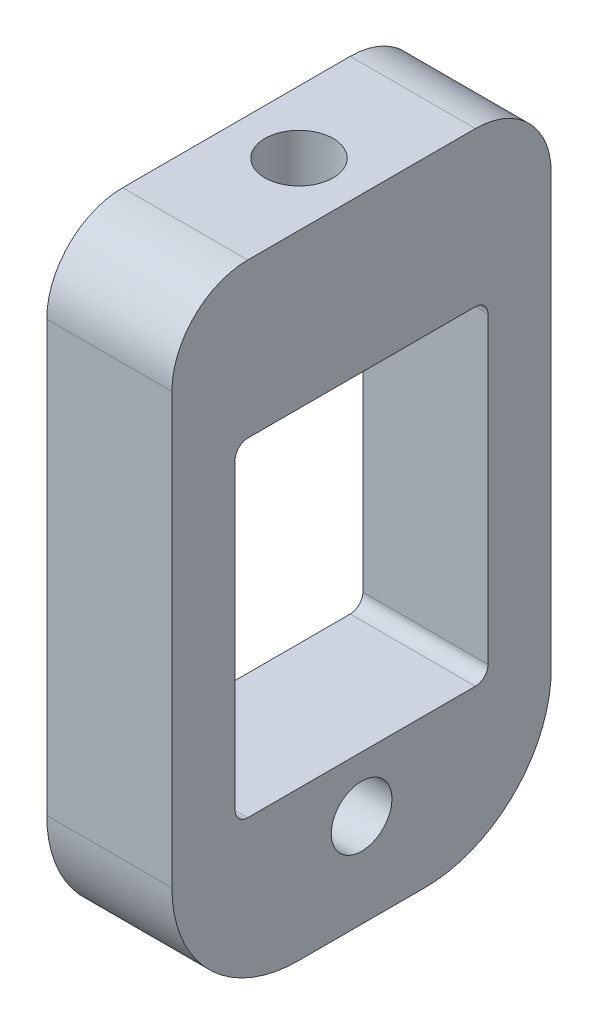
SolidWorks part; units mm, degrees
other "Markup1"
sketch "Sketch6" plane through (-4, 8, -3.5) normal (-0.1216, 0.9914, -0.0475) x (-0.0131, 0.0463, 0.9988)
material "7075 T651 protolabs"
ref_plane "Front Plane" through (0, 0, 0) normal (0, 0, 1) x (1, 0, 0)
ref_plane "Top Plane" through (0, 0, 0) normal (0, 1, 0) x (1, 0, 0)
ref_plane "Right Plane" through (0, 0, 0) normal (1, 0, 0) x (0, 0, -1)
sketch "Sketch16" plane through (0, 0, 0) normal (0, 1, 0) x (1, 0, 0)
  line L1 (-2.475, -7.5) -> (2.475, -7.5)
  line L2 (-2.475, -7.5) -> (-2.475, 7.5)
  line L3 (-2.475, 7.5) -> (2.475, 7.5)
  line L4 (2.475, -7.5) -> (2.475, 7.5)
  line L5 (-2.475, -7.5) -> (2.475, 7.5) construction
  line L6 (-2.475, 7.5) -> (2.475, -7.5) construction
  point P0 (0, 0)
  dimension "D1" = 15
  dimension "D2" = 4.95
extrude "Main Extrude_Locking" add sketch "Sketch16" along normal blind 25
sketch "Sketch18" plane through (-2.475, 0, 0) normal (-1, 0, 0) x (0, 0, 1)
  line L0 (0, 0) -> (0, 2.5) construction
  line L1 (-7.5, 0) -> (7.5, 0) construction
  circle A0 centre (0, 3.7) radius 1.2
  dimension "D2" = 2.4
  dimension "D1" = 2.5
extrude "Cut-Extrude1" cut sketch "Sketch18" against normal up to surface (4.95 mm away) up to face at (2.475, 12.5, 0)
sketch "Sketch8" plane through (-2.475, 0, 0) normal (-1, 0, 0) x (0, 0, 1)
  line L0 (0, 4.9) -> (-7.5, 4.9) construction
  line L1 (-7.5, 25) -> (-7.5, 0) construction
  line L3 (5, 5.9) -> (-5, 5.9)
  line L4 (5, 5.9) -> (5, 18.9)
  line L5 (5, 18.9) -> (-5, 18.9)
  line L6 (-5, 5.9) -> (-5, 18.9)
  line L7 (5, 5.9) -> (-5, 18.9) construction
  line L8 (5, 18.9) -> (-5, 5.9) construction
  circle A0 centre (0, 3.7) radius 1.2 construction
  point P6 (0, 12.4)
  dimension "D1" = 2
  dimension "D2" = 13
  dimension "D3" = 10
extrude "Cut-Extrude2" cut sketch "Sketch8" against normal up to surface (4.95 mm away) up to face at (2.475, 3.7, 1.2)
sketch "Sketch9" plane through (0, 25, 0) normal (0, 1, 0) x (1, 0, 0)
  circle A0 centre (0, 0) radius 1.35
  dimension "D1" = 2.7
extrude "Cut-Extrude3" cut sketch "Sketch9" against normal up to surface (6.1 mm away) up to face at (0, 18.9, 0)
fillet "Fillet1" radius 5 2 edges at (0, 0, 7.5) (0, 0, -7.5)
fillet "Fillet2" radius 3 2 edges at (0, 25, -7.5) (0, 25, 7.5)
fillet "Fillet3" radius 0.5 4 edges at (0, 18.9, 5) (0, 18.9, -5) (0, 5.9, -5) (0, 5.9, 5)
